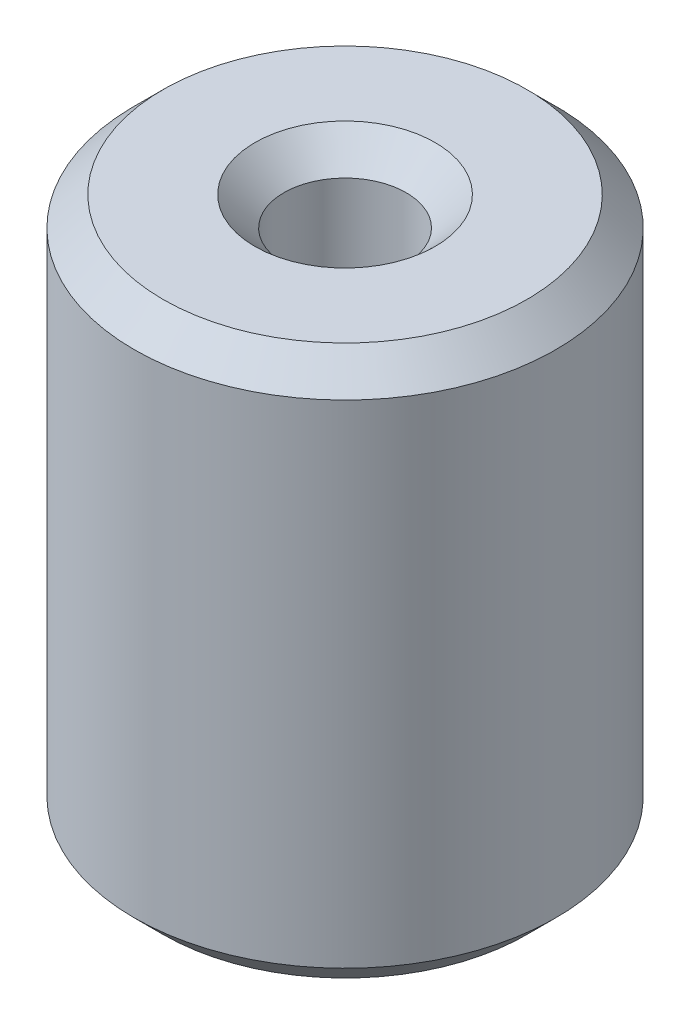
SolidWorks part; units mm, degrees
ref_plane "Front Plane" through (0, 0, 0) normal (0, 0, 1) x (1, 0, 0)
ref_plane "Top Plane" through (0, 0, 0) normal (0, 1, 0) x (1, 0, 0)
ref_plane "Right Plane" through (0, 0, 0) normal (1, 0, 0) x (0, 0, -1)
sketch "Sketch1" plane through (0, 0, 0) normal (0, 1, 0) x (1, 0, 0)
  circle A0 centre (0, 0) radius 5
  dimension "SLEEVE_OD" = 10
extrude "Boss-Extrude1" add sketch "Sketch1" along normal blind 13.0424
sketch "Sketch2" plane through (0, 0, 0) normal (0, 1, 0) x (1, 0, 0)
  circle A0 centre (0, 0) radius 1.4501
  dimension "BORE_D" = 2.9001
extrude "Cut-Extrude1" cut sketch "Sketch2" along normal through all
chamfer "Chamfer1" distance 0.6865 angle 45 4 edges at (0, 13.0424, 1.4501) (0, 0, 1.4501) (0, 0, 5) (0, 13.0424, 5)
